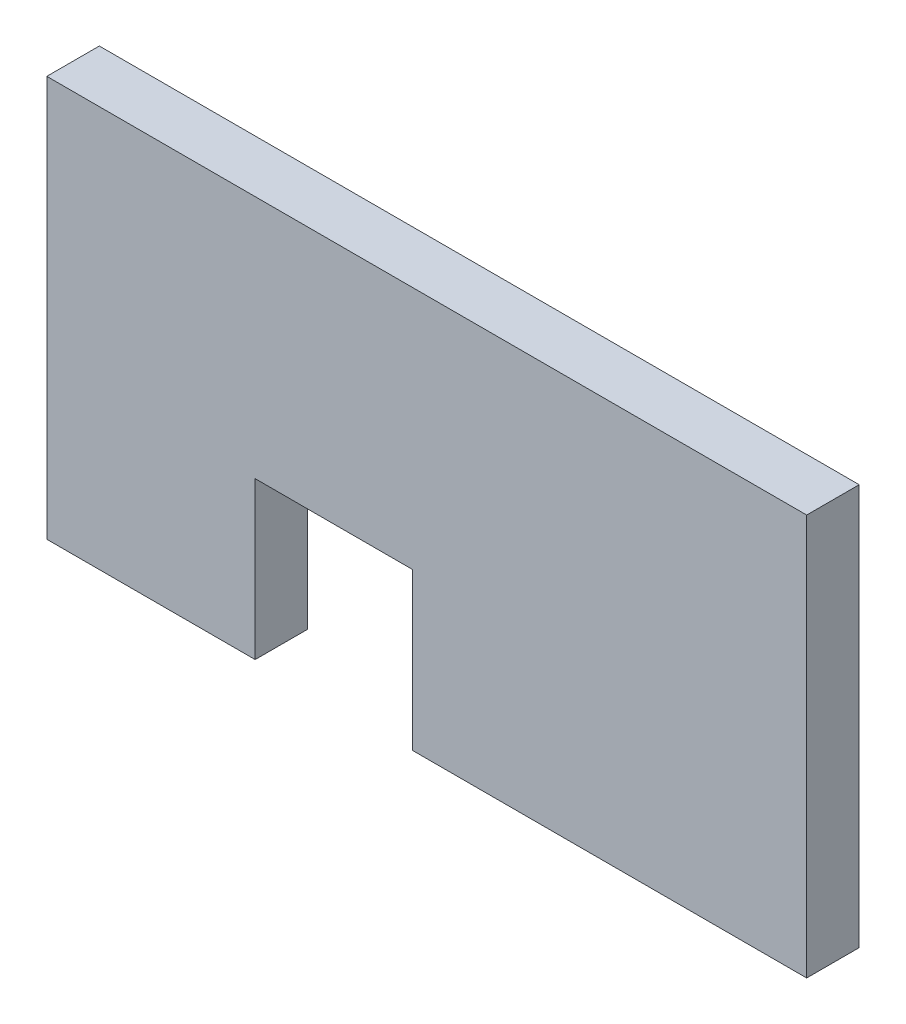
SolidWorks part; units mm, degrees
ref_plane "Front Plane" through (0, 0, 0) normal (0, 0, 1) x (1, 0, 0)
ref_plane "Top Plane" through (0, 0, 0) normal (0, 1, 0) x (1, 0, 0)
ref_plane "Right Plane" through (0, 0, 0) normal (1, 0, 0) x (0, 0, -1)
sketch "Sketch1" plane through (0, 0, 0) normal (0, 0, 1) x (1, 0, 0)
  line L0 (21.7, 33.35) -> (21.7, 15.05) construction
  line L1 (21.7, 37.95) -> (-21.7, 37.95)
  line L2 (21.7, 37.95) -> (21.7, 15.05)
  line L3 (21.7, 15.05) -> (-0.8, 15.05)
  line L4 (-21.7, 37.95) -> (-21.7, 15.05)
  line L5 (-21.7, 33.35) -> (-21.7, 15.05) construction
  line L6 (32.157, 37.95) -> (-32.157, 37.95) construction
  line L7 (28.7, 15.05) -> (-28.7, 15.05) construction
  line L8 (-0.8, 15.05) -> (-0.8, 24) construction
  line L9 (-0.8, 24) -> (-9.8, 24) construction
  line L10 (-9.8, 24) -> (-9.8, 15.05) construction
  line L11 (-0.8, 15.05) -> (-0.8, 24)
  line L12 (-0.8, 24) -> (-9.8, 24)
  line L13 (-9.8, 24) -> (-9.8, 15.05)
  line L14 (-9.8, 15.05) -> (-21.7, 15.05)
sketch "Sketch2" plane through (0, 0, 0) normal (1, 0, 0) x (0, 0, -1)
  line L0 (0, 19.65) -> (0, 37.95) construction
  line L1 (0, 37.95) -> (-3, 37.95)
  line L2 (0, 37.95) -> (0, 15.05)
  line L3 (0, 15.05) -> (-3, 15.05)
  line L4 (-3, 37.95) -> (-3, 15.05)
  line L5 (-3, 19.65) -> (-3, 34.95) construction
  line L6 (-53.857, 15.05) -> (10.457, 15.05) construction
  line L7 (-50.4, 37.95) -> (7, 37.95) construction
extrude "Boss-Extrude1" add sketch "Sketch1" along normal up to vertex (3 mm away) up to point (0, 37.95, 3)
